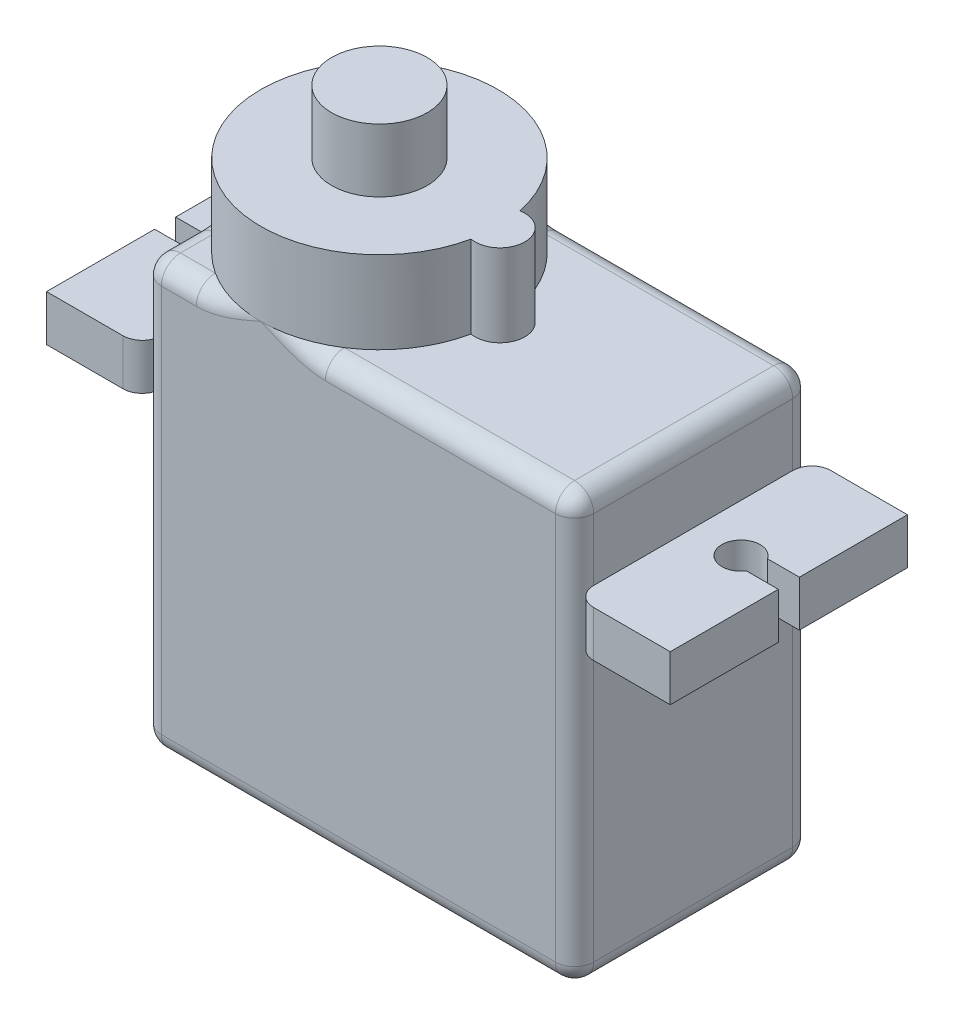
SolidWorks part; units mm, degrees
ref_plane "Front Plane" through (0, 0, 0) normal (0, 0, 1) x (1, 0, 0)
ref_plane "Top Plane" through (0, 0, 0) normal (0, 1, 0) x (1, 0, 0)
ref_plane "Right Plane" through (0, 0, 0) normal (1, 0, 0) x (0, 0, -1)
sketch "Sketch1" plane through (0, 0, 0) normal (0, 1, 0) x (1, 0, 0)
  line L1 (-11.3, -6.2) -> (11.3, -6.2)
  line L2 (-11.3, -6.2) -> (-11.3, 6.2)
  line L3 (-11.3, 6.2) -> (11.3, 6.2)
  line L4 (11.3, -6.2) -> (11.3, 6.2)
  line L5 (-11.3, -6.2) -> (11.3, 6.2) construction
  line L6 (-11.3, 6.2) -> (11.3, -6.2) construction
  point P0 (0, 0)
  dimension "D1" = 22.6
  dimension "D2" = 12.4
extrude "Boss-Extrude1" add sketch "Sketch1" along normal blind 22.3
sketch "Sketch2" plane through (11.3, 0, 0) normal (1, 0, 0) x (0, 0, -1)
  line L0 (-6.2, 22.3) -> (-6.2, 0) construction
  line L1 (-6.2, 18.05) -> (6.2, 18.05)
  line L2 (-6.2, 18.05) -> (-6.2, 15.65)
  line L3 (-6.2, 15.65) -> (6.2, 15.65)
  line L4 (6.2, 18.05) -> (6.2, 15.65)
  line L5 (6.2, 22.3) -> (6.2, 0) construction
  line L6 (-6.2, 22.3) -> (6.2, 22.3) construction
  dimension "D1" = 2.4
  dimension "D2" = 4.25
extrude "Boss-Extrude2" add sketch "Sketch2" along normal blind 5 separate body
sketch "Sketch3" plane through (-11.3, 0, 0) normal (-1, 0, 0) x (0, 0, 1)
  line L0 (-6.2, 22.3) -> (-6.2, 0) construction
  line L1 (-6.2, 18.05) -> (6.2, 18.05)
  line L2 (-6.2, 18.05) -> (-6.2, 15.65)
  line L3 (-6.2, 15.65) -> (6.2, 15.65)
  line L4 (6.2, 18.05) -> (6.2, 15.65)
  line L5 (6.2, 22.3) -> (6.2, 0) construction
  line L6 (-6.2, 22.3) -> (6.2, 22.3) construction
  dimension "D1" = 2.4
  dimension "D2" = 4.25
extrude "Boss-Extrude3" add sketch "Sketch3" along normal blind 5 separate body
sketch "Sketch4" plane through (0, 18.05, 0) normal (0, 1, 0) x (1, 0, 0)
  line L3 (16.3, 0) -> (-16.3, 0) construction
  line L4 (16.3, 6.2) -> (16.3, 0.55) construction
  line L5 (-16.3, -6.2) -> (-16.3, -0.55) construction
  line L6 (-16.3, 0.55) -> (-14.6352, 0.55)
  line L7 (-16.3, 0.55) -> (-16.3, -0.55)
  line L8 (-16.3, -0.55) -> (-14.6352, -0.55)
  line L9 (0, 0) -> (0, 6.2) construction
  line L10 (11.3, 6.2) -> (-11.3, 6.2) construction
  line L11 (16.3, -0.55) -> (14.6352, -0.55)
  line L12 (16.3, 0.55) -> (16.3, -0.55)
  line L13 (16.3, 0.55) -> (14.6352, 0.55)
  arc A1 (-14.6352, -0.55) -> (-14.6352, 0.55) centre (-13.8, 0) ccw
  arc A2 (14.6352, -0.55) -> (14.6352, 0.55) centre (13.8, 0) cw
  dimension "D1" = 2
  dimension "D2" = 1.1
  dimension "D3" = 0.55
  dimension "D4" = 2.5
extrude "Cut-Extrude1" cut sketch "Sketch4" against normal blind 5
sketch "Sketch5" plane through (0, 22.3, 0) normal (0, 1, 0) x (1, 0, 0)
  line L0 (0, 0) -> (-11.3, 0) construction
  line L1 (-11.3, -6.2) -> (-11.3, 6.2) construction
  arc A2 (0.9667, 1.2789) -> (0.9667, -1.2789) centre (-5.1, 0) ccw
  arc A3 (0.9667, -1.2789) -> (0.9667, 1.2789) centre (1.2, 0) ccw
  dimension "D4" = 6.2
  dimension "D1" = 1.2
  dimension "D2" = 6.3
  dimension "D3" = 6.2
extrude "Boss-Extrude4" add sketch "Sketch5" along normal blind 4.3
sketch "Sketch6" plane through (0, 26.6, 0) normal (0, 1, 0) x (1, 0, 0)
  circle A0 centre (-5.1, 0) radius 2.5
  dimension "D1" = 5
extrude "Boss-Extrude5" add sketch "Sketch6" along normal blind 3.3
sketch "Sketch7" plane through (-11.3, 0, 0) normal (-1, 0, 0) x (0, 0, 1)
  circle A0 centre (0, 4.5) radius 0.6
  circle A1 centre (-1.2, 4.5) radius 0.6
  circle A2 centre (1.2, 4.5) radius 0.6
  dimension "D1" = 1.2
  dimension "D2" = 4.5
extrude "Boss-Extrude6" add sketch "Sketch7" along normal blind 2.3 separate body contours A1 | A0 | A2 region at (-11.3, 4.5, 0) region at (-11.3, 4.5, -1.2) region at (-11.3, 4.5, 1.2)
fillet "Fillet1" radius 1 15 edges at (-11.3, 22.3, 3.1) (-8.2, 22.3, -6.2) (-8.2, 22.3, 6.2) (-11.3, 0, 0) (0, 0, -6.2) (0, 0, 6.2) (11.3, 0, 0) (11.3, 11.15, -6.2) (11.3, 11.15, 6.2) (-11.3, 11.15, -6.2) (-11.3, 11.15, 6.2) (-11.3, 22.3, -3.1) (3.1, 22.3, -6.2) (11.3, 22.3, 0) (3.1, 22.3, 6.2)
fillet "Fillet2" radius 1 2 edges at (-11.3, 16.85, -6.2) (-11.3, 16.85, 6.2)
fillet "Fillet3" radius 1 2 edges at (11.3, 16.85, 6.2) (11.3, 16.85, -6.2)
